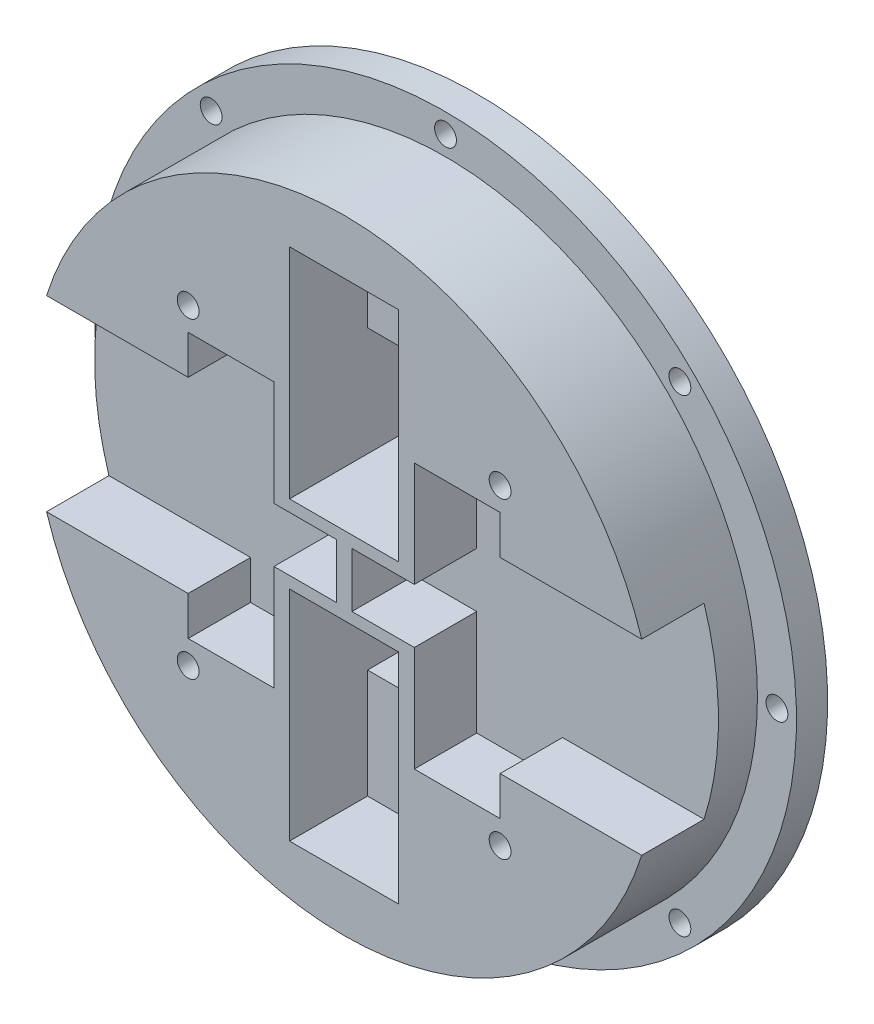
SolidWorks part; units mm, degrees
ref_plane "Front Plane" through (0, 0, 0) normal (0, 0, 1) x (1, 0, 0)
ref_plane "Top Plane" through (0, 0, 0) normal (0, 1, 0) x (1, 0, 0)
ref_plane "Right Plane" through (0, 0, 0) normal (1, 0, 0) x (0, 0, -1)
sketch "Sketch1" plane through (0, 0, 0) normal (0, 0, 1) x (1, 0, 0)
  circle A0 centre (0, 0) radius 40
extrude "Boss-Extrude1" add sketch "Sketch1" along normal blind 13
ref_plane "Plane1" through (0, 0, 13) normal (0, 0, 1) x (1, 0, 0)
sketch "Sketch2" plane through (0, 0, 13) normal (0, 0, 1) x (1, 0, 0)
  line L0 (-40, 0) -> (40, 0)
  line L14 (0, 4) -> (0, -4)
  line L17 (0, 40) -> (0, -40)
  line L40 (19.0101, 19.0101) -> (-19.0101, -19.0101) construction
  line L41 (19.0101, -19.0101) -> (-19.0101, 19.0101) construction
  line L51 (-1, 3.5) -> (-1, -3.5)
  line L52 (-20, 17) -> (-9, 17)
  line L53 (-9, 17) -> (-9, 3.5)
  line L54 (-20, -12) -> (-40, -12)
  line L55 (-40, 12) -> (-40, -12)
  line L56 (-40, 12) -> (-20, 12)
  line L57 (-20, 17) -> (-20, 12)
  line L58 (-20, -17) -> (-9, -17)
  line L62 (-20, -12) -> (-20, -17)
  line L63 (20, -12) -> (40, -12)
  line L64 (20, -12) -> (20, -17)
  line L65 (20, -17) -> (9, -17)
  line L66 (9, -3.5) -> (9, -17)
  line L67 (1, -3.5) -> (9, -3.5)
  line L69 (1, 3.5) -> (1, -3.5)
  line L70 (9, 3.5) -> (1, 3.5)
  line L71 (9, 17) -> (9, 3.5)
  line L72 (20, 17) -> (9, 17)
  line L73 (20, 17) -> (20, 12)
  line L74 (40, 12) -> (20, 12)
  line L75 (-1, -3.5) -> (-9, -3.5)
  line L76 (-9, -3.5) -> (-9, -17)
  line L77 (-9, 3.5) -> (-1, 3.5)
  line L78 (40, 12) -> (40, -12)
  circle A0 centre (0, 0) radius 40 construction
  circle A1 centre (-20, 20) radius 1.4
  circle A2 centre (20, 20) radius 1.4
  circle A3 centre (-20, -20) radius 1.4
  circle A4 centre (20, -20) radius 1.4
  point P25 (0, 0)
  point P44 (-1, 0)
  dimension "D8" = 40
  dimension "D1" = 7
  dimension "D2" = 11
  dimension "D3" = 8
  dimension "D4" = 1
  dimension "D5" = 20
  dimension "D6" = 40
  dimension "D7" = 40
  dimension "D9" = 40
  dimension "D10" = 24
  dimension "D11" = 12
  dimension "D12" = 34
  dimension "D13" = 17
extrude "Cut-Extrude1" cut sketch "Sketch2" against normal blind 8 contours L0 L14 | L14 L70 L0 | L0 | L0 | L14 L0 | L0 | L0 L70 | L73 L14 L0 | L67 L66 L65 L64 L63 L78 L74 L73 L72 L71 L70 L69 region at (-22.0912, 6.7659, 13) region at (22.0912, 6.7659, 13) region at (22.0912, -6.7659, 13) region at (-22.0912, -6.7659, 13)
extrude "Cut-Extrude2" cut sketch "Sketch2<4>" against normal blind 5 contours A2 | A3 | A4 | A1 region at (20, 20, 13) region at (-20, -20, 13) region at (20, -20, 13)
sketch "Sketch2<4>" plane through (0, 0, 13) normal (0, 0, 1) x (1, 0, 0) same geometry as "Sketch2"
sketch "Sketch3" plane through (0, 0, 13) normal (0, 0, 1) x (1, 0, 0)
  line L0 (0, 40) -> (0, -40)
  line L1 (-40, 0) -> (40, 0)
  line L2 (-7, -5) -> (7, -5)
  line L7 (-7, -5) -> (-7, -33)
  line L8 (-7, -33) -> (7, -33)
  line L9 (7, -33) -> (7, -5)
  line L10 (-7, 33) -> (7, 33)
  line L11 (-7, 5) -> (-7, 33)
  line L12 (-7, 5) -> (7, 5)
  line L13 (7, 33) -> (7, 5)
  arc A0 (38.1576, 12) -> (-38.1576, 12) centre (0, 0) ccw construction
  arc A1 (-38.1576, -12) -> (38.1576, -12) centre (0, 0) ccw construction
  arc A2 (-38.1576, 12) -> (-38.1576, -12) centre (0, 0) ccw construction
  arc A3 (38.1576, -12) -> (38.1576, 12) centre (0, 0) ccw construction
  dimension "D1" = 5
  dimension "D2" = 14
  dimension "D3" = 28
extrude "Cut-Extrude6" cut sketch "Sketch3" against normal blind 10 contours L8 L9 L2 L0 | L10 L13 L12 L11 | L9 L2 L7 L8 region at (3.5, -19, 13)
ref_plane "Plane2" through (0, 0, 0) normal (0, 0, -1) x (-1, 0, 0)
sketch "Sketch5" plane through (0, 0, 0) normal (0, 0, -1) x (-1, 0, 0)
  circle A0 centre (0, 0) radius 45
  dimension "D1" = 90
extrude "Boss-Extrude2" add sketch "Sketch5" along normal blind 4
sketch "Sketch6" plane through (0, 0, 0) normal (0, 0, -1) x (-1, 0, 0)
  circle A0 centre (0, 0) radius 42.5
  circle A1 centre (0, 42.5) radius 1.4
  circle A2 centre (30.052, 30.052) radius 1.4
  circle A3 centre (42.5, 0) radius 1.4
  circle A4 centre (30.052, -30.052) radius 1.4
  circle A5 centre (0, -42.5) radius 1.4
  circle A6 centre (-30.052, -30.052) radius 1.4
  circle A7 centre (-42.5, 0) radius 1.4
  circle A8 centre (-30.052, 30.052) radius 1.4
  circle A9 centre (0, 0) radius 32.5
  circle A10 centre (0, 32.5) radius 1.4
  circle A11 centre (22.981, 22.981) radius 1.4
  circle A12 centre (32.5, 0) radius 1.4
  circle A13 centre (22.981, -22.981) radius 1.4
  circle A14 centre (0, -32.5) radius 1.4
  circle A15 centre (-22.981, -22.981) radius 1.4
  circle A16 centre (-32.5, 0) radius 1.4
  circle A17 centre (-22.981, 22.981) radius 1.4
  point P21 (0, 0)
  point P40 (0, 0)
  dimension "D1" = 85
  dimension "D2" = 8
  dimension "D3" = 65
  dimension "D4" = 8
extrude "Cut-Extrude8" cut sketch "Sketch6" along normal blind 4 contours A8 | A1 | A2 | A3 | A4 | A5 | A6 | A7
extrude "Cut-Extrude9" cut sketch "Sketch6<3>" along normal blind 4 contours A10 | A11 | A12 | A13 | A14 | A15 | A16 | A17
sketch "Sketch6<3>" plane through (0, 0, 0) normal (0, 0, -1) x (-1, 0, 0) same geometry as "Sketch6"
sketch "Sketch7" plane through (0, 0, 13) normal (0, 0, 1) x (1, 0, 0)
  line L0 (-7, 19) -> (-7, 5)
  line L1 (-7, 5) -> (-7, 33) construction
  line L2 (-7, 5) -> (7, 5)
  line L3 (7, 5) -> (7, 19)
  line L4 (7, 33) -> (7, 5) construction
  line L5 (7, 19) -> (-7, 19)
  line L6 (-40, 0) -> (40, 0)
  line L7 (7, -5) -> (7, -19)
  line L8 (-7, -5) -> (7, -5)
  line L9 (-7, -19) -> (-7, -5)
  line L10 (7, -19) -> (-7, -19)
  arc A0 (-38.1576, 12) -> (-38.1576, -12) centre (0, 0) ccw construction
  arc A1 (38.1576, -12) -> (38.1576, 12) centre (0, 0) ccw construction
  dimension "D1" = 5
extrude "Cut-Extrude10" cut sketch "Sketch7" against normal blind 17 contours L3 L5 L0 L2 | L10 L7 L8 L9 | L5 L0 L2 L3 | L7 L10 L9 L8 region at (0, 12, 13) region at (0, -12, 13)
